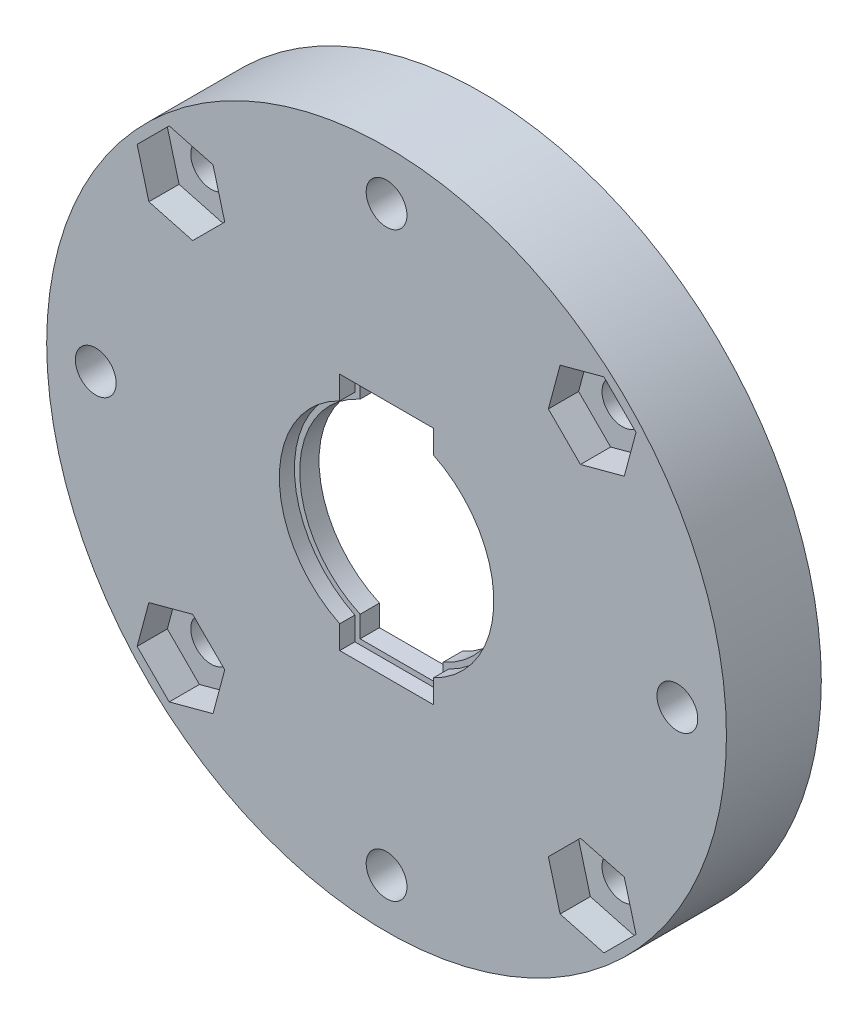
SolidWorks part; units mm, degrees
ref_plane "Front Plane" through (0, 0, 0) normal (0, 0, 1) x (1, 0, 0)
ref_plane "Top Plane" through (0, 0, 0) normal (0, 1, 0) x (1, 0, 0)
ref_plane "Right Plane" through (0, 0, 0) normal (1, 0, 0) x (0, 0, -1)
ref_axis "Z" through (0, 0, -6.594) along (0, 0, 1)
sketch "Sketch3" plane through (0, 0, 0) normal (0, 0, 1) x (1, 0, 0)
  line L0 (-3.1, -6.3875) -> (-3.1, -7.9247)
  line L1 (-3.1, -7.9247) -> (3.1, -7.9247)
  line L2 (3.1, -7.9247) -> (3.1, -6.3875)
  line L3 (3.1, 6.3875) -> (3.1, 7.9244)
  line L4 (3.1, 7.9244) -> (-3.1, 7.9244)
  line L5 (-3.1, 7.9244) -> (-3.1, 6.3875)
  line L132 (3.05, 6.3548) -> (3.05, 6.3561) construction
  line L133 (-3.05, 6.3561) -> (-3.05, 6.3548) construction
  line L134 (3.05, -6.3561) -> (3.05, -6.355) construction
  line L135 (-3.05, -6.355) -> (-3.05, -6.3561) construction
  line L198 (3.05, 6.3548) -> (3.05, 7.8744)
  line L199 (3.05, 7.8744) -> (-3.05, 7.8744)
  line L200 (-3.05, 7.8744) -> (-3.05, 6.3548)
  line L201 (-3.05, 6.3548) -> (-3.4914, 6.1247)
  line L202 (-3.4914, 6.1247) -> (-3.9416, 5.8451)
  line L203 (-3.9416, 5.8451) -> (-4.3696, 5.5325)
  line L204 (-4.3696, 5.5325) -> (-4.7729, 5.1886)
  line L205 (-4.7729, 5.1886) -> (-5.1492, 4.8154)
  line L206 (-5.1492, 4.8154) -> (-5.4964, 4.4149)
  line L207 (-5.4964, 4.4149) -> (-5.8125, 3.9896)
  line L208 (-5.8125, 3.9896) -> (-6.0958, 3.5417)
  line L209 (-6.0958, 3.5417) -> (-6.3446, 3.0737)
  line L210 (-6.3446, 3.0737) -> (-6.5576, 2.5884)
  line L211 (-6.5576, 2.5884) -> (-6.7335, 2.0885)
  line L212 (-6.7335, 2.0885) -> (-6.8714, 1.5768)
  line L213 (-6.8714, 1.5768) -> (-6.9705, 1.0561)
  line L214 (-6.9705, 1.0561) -> (-7.0301, 0.5295)
  line L215 (-7.0301, 0.5295) -> (-7.05, -0.0001)
  line L216 (-7.05, -0.0001) -> (-7.0301, -0.5297)
  line L217 (-7.0301, -0.5297) -> (-6.9705, -1.0563)
  line L218 (-6.9705, -1.0563) -> (-6.8714, -1.577)
  line L219 (-6.8714, -1.577) -> (-6.7335, -2.0887)
  line L220 (-6.7335, -2.0887) -> (-6.5576, -2.5887)
  line L221 (-6.5576, -2.5887) -> (-6.3446, -3.074)
  line L222 (-6.3446, -3.074) -> (-6.0958, -3.5419)
  line L223 (-6.0958, -3.5419) -> (-5.8125, -3.9898)
  line L224 (-5.8125, -3.9898) -> (-5.4964, -4.4152)
  line L225 (-5.4964, -4.4152) -> (-5.1492, -4.8156)
  line L226 (-5.1492, -4.8156) -> (-4.7729, -5.1888)
  line L227 (-4.7729, -5.1888) -> (-4.3696, -5.5327)
  line L228 (-4.3696, -5.5327) -> (-3.9416, -5.8453)
  line L229 (-3.9416, -5.8453) -> (-3.4914, -6.1249)
  line L230 (-3.4914, -6.1249) -> (-3.05, -6.355)
  line L231 (-3.05, -6.355) -> (-3.05, -7.8747)
  line L232 (-3.05, -7.8747) -> (3.05, -7.8747)
  line L233 (3.05, -7.8747) -> (3.05, -6.355)
  line L234 (3.05, -6.355) -> (3.4914, -6.1249)
  line L235 (3.4914, -6.1249) -> (3.9417, -5.8453)
  line L236 (3.9417, -5.8453) -> (4.3696, -5.5327)
  line L237 (4.3696, -5.5327) -> (4.7729, -5.1888)
  line L238 (4.7729, -5.1888) -> (5.1492, -4.8156)
  line L239 (5.1492, -4.8156) -> (5.4964, -4.4152)
  line L240 (5.4964, -4.4152) -> (5.8125, -3.9898)
  line L241 (5.8125, -3.9898) -> (6.0958, -3.5419)
  line L242 (6.0958, -3.5419) -> (6.3447, -3.074)
  line L243 (6.3447, -3.074) -> (6.5576, -2.5887)
  line L244 (6.5576, -2.5887) -> (6.7336, -2.0887)
  line L245 (6.7336, -2.0887) -> (6.8714, -1.577)
  line L246 (6.8714, -1.577) -> (6.9705, -1.0563)
  line L247 (6.9705, -1.0563) -> (7.0301, -0.5297)
  line L248 (7.0301, -0.5297) -> (7.05, -0.0001)
  line L249 (7.05, -0.0001) -> (7.0301, 0.5295)
  line L250 (7.0301, 0.5295) -> (6.9705, 1.0561)
  line L251 (6.9705, 1.0561) -> (6.8714, 1.5768)
  line L252 (6.8714, 1.5768) -> (6.7336, 2.0885)
  line L253 (6.7336, 2.0885) -> (6.5576, 2.5884)
  line L254 (6.5576, 2.5884) -> (6.3447, 3.0737)
  line L255 (6.3447, 3.0737) -> (6.0958, 3.5417)
  line L256 (6.0958, 3.5417) -> (5.8125, 3.9896)
  line L257 (5.8125, 3.9896) -> (5.4964, 4.4149)
  line L258 (5.4964, 4.4149) -> (5.1492, 4.8154)
  line L259 (5.1492, 4.8154) -> (4.7729, 5.1886)
  line L260 (4.7729, 5.1886) -> (4.3696, 5.5325)
  line L261 (4.3696, 5.5325) -> (3.9417, 5.8451)
  line L262 (3.9417, 5.8451) -> (3.4914, 6.1247)
  line L263 (3.4914, 6.1247) -> (3.05, 6.3548)
  line L264 (3.05, 6.3561) -> (3.05, 7.8744) construction
  line L265 (3.05, 7.8744) -> (-3.05, 7.8744) construction
  line L266 (-3.05, 7.8744) -> (-3.05, 6.3561) construction
  line L297 (-3.05, -6.3561) -> (-3.05, -7.8747) construction
  line L298 (-3.05, -7.8747) -> (3.05, -7.8747) construction
  line L299 (3.05, -7.8747) -> (3.05, -6.3561) construction
  arc A1 (-3.05, 6.3561) -> (-3.05, -6.3561) centre (0, 0) ccw construction
  arc A2 (3.05, 6.3561) -> (-3.05, 6.3561) centre (0, 0) ccw construction
  arc A3 (3.05, -6.3561) -> (3.05, 6.3561) centre (0, 0) ccw construction
  arc A4 (-3.05, -6.3561) -> (3.05, -6.3561) centre (0, 0) ccw construction
  circle A5 centre (0, 0) radius 22.5
  arc A6 (-3.1, 6.3875) -> (-3.1, -6.3875) centre (0, 0) ccw
  arc A7 (3.1, -6.3875) -> (3.1, 6.3875) centre (0, 0) ccw
  dimension "D1" = 14.1
  dimension "D3" = 45
  dimension "D2" = 0.05
  dimension "D4" = 0.05
extrude "Boss-Extrude2" add sketch "Sketch3" against normal blind 1
sketch "Sketch4" plane through (0, 0, -1) normal (0, 0, -1) x (-1, 0, 0)
  line L39 (2.75, 6.1644) -> (2.75, 7.5744)
  line L40 (2.75, 7.5744) -> (-2.75, 7.5744)
  line L41 (-2.75, 7.5744) -> (-2.75, 6.1644)
  line L42 (-2.75, -6.1644) -> (-2.75, -7.5747)
  line L43 (-2.75, -7.5747) -> (2.75, -7.5747)
  line L44 (2.75, -7.5747) -> (2.75, -6.1644)
  circle A14 centre (0, 0) radius 22.5
  arc A17 (-2.75, 6.1644) -> (-2.75, -6.1644) centre (0, 0) ccw
  arc A18 (2.75, -6.1644) -> (2.75, 6.1644) centre (0, 0) ccw
  dimension "D1" = 45
extrude "Boss-Extrude3" add sketch "Sketch4" along normal blind 5.28
sketch "Sketch5" plane through (0, 0, -6.28) normal (0, 0, -1) x (-1, 0, 0)
  circle A0 centre (0, 0) radius 17.25
  dimension "D1" = 34.5
extrude "Cut-Extrude1" cut sketch "Sketch5" against normal blind 4
sketch "Sketch6" plane through (0, 0, 0) normal (0, 0, 1) x (1, 0, 0)
  line L0 (0, 0) -> (13.6118, 13.6118) construction
  line L1 (-16.3801, 0) -> (0, 0) construction
  line L3 (14.3888, 16.5117) -> (11.4889, 15.7347)
  line L4 (11.4889, 15.7347) -> (10.7119, 12.8348)
  line L5 (10.7119, 12.8348) -> (12.8348, 10.7119)
  line L6 (12.8348, 10.7119) -> (15.7347, 11.4889)
  line L7 (15.7347, 11.4889) -> (16.5117, 14.3888)
  line L8 (16.5117, 14.3888) -> (14.3888, 16.5117)
  circle A0 centre (13.6118, 13.6118) radius 2.6 construction
  dimension "D1" = 135
  dimension "D2" = 19.25
  dimension "D3" = 5.2
extrude "Cut-Extrude2" cut sketch "Sketch6" against normal blind 2
sketch "Sketch8" plane through (0, 0, 0) normal (0, 0, 1) x (1, 0, 0)
  line L0 (36.6653, 0) -> (49.0214, 0) construction
  line L1 (0, 0) -> (13.6118, 13.6118) construction
  circle A0 centre (0, 0) radius 19.25 construction
  circle A1 centre (13.6118, 13.6118) radius 1.35
  dimension "D1" = 38.5
  dimension "D3" = 2.7
  dimension "D2" = 135
extrude "Cut-Extrude4" cut sketch "Sketch8" against normal through all
pattern_circular "CirPattern1" count 4 over 360 about axis through (0, 0, -6.594) along (0, 0, 1) of "Cut-Extrude2", "Cut-Extrude4"
ref_plane "Plane4" through (0, 0, 0) normal (-0.7071, 0.7071, 0) x (0, 0, 1)
pattern_circular "CirPattern2" count 8 over 360 about axis through (0, 0, -6.594) along (0, 0, 1) of "Cut-Extrude4"
equation "\"BearingBaseDistance\"= 10"
equation "\"BearingOD\"= 32"
equation "\"BearingID\" = 25"
equation "\"BearingHeight\"= 4"
equation "\"SeatsOD\"= \"BearingOD\" + 10"
equation "\"WireHarnessHeight\"= 4"
equation "\"OuterWallWidth\"= 6"
equation "\"OverallOD\" = 45"
equation "\"OuterHousingHeight\" = \"WireHarnessHeight\" + \"BearingHeight\"*2 + \"BearingBaseDistance\""
equation "\"RetainingRingThickness\" = 1.30"
equation "\"RetaininRingGrooveDiameter\" = 23.9"
equation "\"ShaftLengthAfterFlange\" = 2*\"BearingHeight\" + \"BearingBaseDistance\" + \"RetainingRingThickness\"*2\t'give a retaining ring thickness of extra clearance"
equation "\"RetainingRingGrooveBase\" = \"ShaftLengthAfterFlange\" - \"RetainingRingThickness\"*2"
equation "\"CoverThickness\" = 1"
equation "\"CoverClearance\" = 1"
equation "\"FlangHeight\" = 3"
equation "\"PCBWidth\" = 5"
equation "\"PCBHeight\" = \"OuterHousingHeight\" "
equation "\"PCBThickness\" = 1"
equation "\"NormalDistSidewallPCBToZ\" = (\"OverallOD\"/2) - 1.6\t'radial distance from the z axis to pcb origin on the top/connector side"
equation "\"PCBSidewallCutoutClearance\" = 0.1"
equation "\"OutputHubBoltCircleRadius\" = 8"
equation "\"OutputHubOD\" = 27"
equation "\"StatorWireRadius\" = \"NormalDistSidewallPCBToZ\" - 5.7"
equation "\"MountingHoleRadius\" = (\"OverallOD\"+\"BearingOD\")/4"
equation "\"D3@Sketch3\"=\"OverallOD\""
equation "\"D1@Sketch4\"=\"OverallOD\""
equation "\"D1@Sketch8\"=\"MountingHoleRadius\"*2"
equation "\"D2@Sketch6\"=(\"OverallOD\"+\"BearingOD\")/4"
